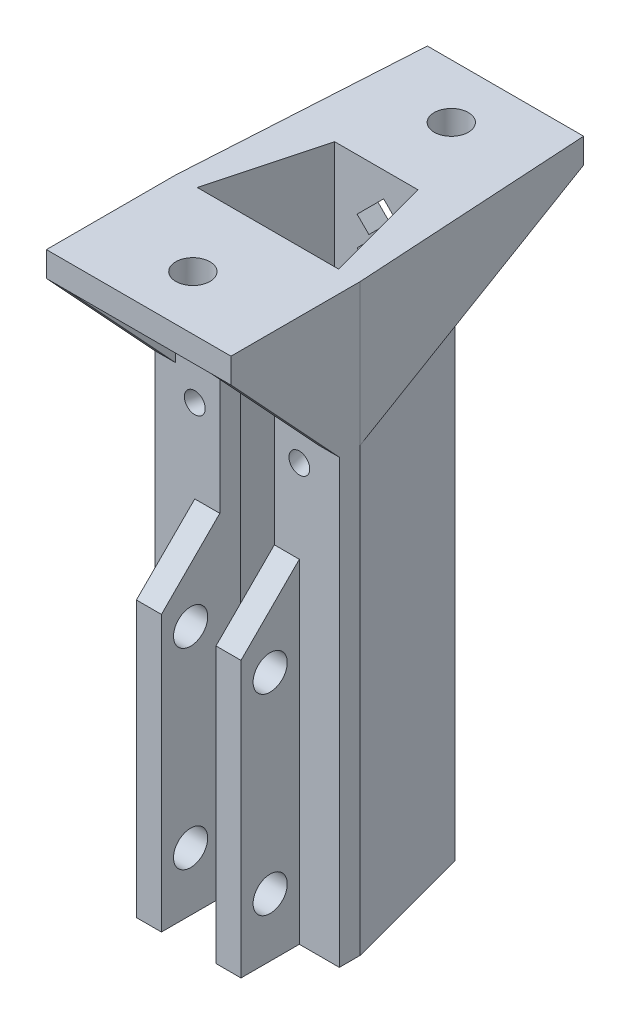
SolidWorks part; units mm, degrees
ref_plane "Front Plane" through (0, 0, 0) normal (0, 0, 1) x (1, 0, 0)
ref_plane "Top Plane" through (0, 0, 0) normal (0, 1, 0) x (1, 0, 0)
ref_plane "Right Plane" through (0, 0, 0) normal (1, 0, 0) x (0, 0, -1)
sketch "Sketch2" plane through (0, 0, 0) normal (0, 1, 0) x (1, 0, 0)
  line L0 (-8.0683, 3.8436) -> (5.7683, 3.8436)
  line L1 (-8.0683, 3.8436) -> (-8.0683, 1.3436)
  line L2 (5.7683, 3.8436) -> (5.7683, 1.3436)
  line L3 (-8.0683, 1.3436) -> (5.7683, 1.3436)
  line L4 (5.7683, 3.8436) -> (9.9215, -11.6564)
  line L5 (5.7683, 3.8436) -> (3.3535, 3.1965)
  line L6 (9.9215, -11.6564) -> (7.5067, -12.3035)
  line L7 (3.3535, 3.1965) -> (7.5067, -12.3035)
  line L8 (-8.0683, 3.8436) -> (-12.2215, -11.6564)
  line L9 (-8.0683, 3.8436) -> (-5.6535, 3.1965)
  line L10 (-12.2215, -11.6564) -> (-9.8067, -12.3035)
  line L11 (-5.6535, 3.1965) -> (-9.8067, -12.3035)
  line L12 (-12.2215, -11.6564) -> (-4.4215, -11.6564)
  line L13 (-12.2215, -11.6564) -> (-12.2215, -14.1564)
  line L14 (-4.4215, -11.6564) -> (-4.4215, -14.1564)
  line L15 (-12.2215, -14.1564) -> (-4.4215, -14.1564)
  line L16 (9.9215, -11.6564) -> (2.1215, -11.6564)
  line L17 (9.9215, -11.6564) -> (9.9215, -14.1564)
  line L18 (2.1215, -11.6564) -> (2.1215, -14.1564)
  line L19 (9.9215, -14.1564) -> (2.1215, -14.1564)
  line L20 (-4.4215, -14.1564) -> (-7.4215, -14.1564)
  line L21 (-4.4215, -14.1564) -> (-4.4215, -21.1564)
  line L22 (-7.4215, -14.1564) -> (-7.4215, -21.1564)
  line L23 (-4.4215, -21.1564) -> (-7.4215, -21.1564)
  line L24 (2.1215, -14.1564) -> (5.1215, -14.1564)
  line L25 (2.1215, -14.1564) -> (2.1215, -21.1564)
  line L26 (5.1215, -14.1564) -> (5.1215, -21.1564)
  line L27 (2.1215, -21.1564) -> (5.1215, -21.1564)
  point P0 (-6.15, 1.3436)
  point P21 (3.85, 1.3436)
  point P24 (7.3334, -11.6564)
  point P25 (-9.6333, -11.6564)
  dimension "D1" = 0
  dimension "D2" = 2.5
  dimension "D3" = 2.5
  dimension "D4" = 2.5
  dimension "D5" = 10
  dimension "D6" = 360
  dimension "D7" = 13
  dimension "D8" = 2.5
  dimension "D9" = 2.5
  dimension "D10" = 13
  dimension "D11" = 3
  dimension "D12" = 3
  dimension "D13" = 105
  dimension "D14" = 7.8
  dimension "D15" = 7.8
  dimension "D16" = 105
  dimension "D17" = 16.9667
  dimension "D18" = 6.5431
  dimension "D19" = 7
  dimension "D20" = 7
extrude "Boss-Extrude1" add sketch "Sketch2" along normal blind 40 contours L16 L4 L2 L3 L7 | L9 L11 L3 L7 L5 L0 | L8 L12 L11 L3 L1 | L5 L7 L3 L2 | L11 L9 L1 L3 | L13 L15 L14 L12 L11 L10 | L12 L10 L11 | L6 L16 L7 | L19 L17 L6 L7 L16 L18 | L25 L27 L26 L19 | L23 L21 L15 L22 region at (-7.0264, 0, -2.4857) region at (-9.164, 0, 4.9784) region at (-1.15, 0, -2.635) region at (6.8641, 0, 4.9784) region at (4.7264, 0, -2.4857) region at (-10.5538, 0, 11.8721) region at (-8.2214, 0, 12.9528) region at (5.9214, 0, 12.9528) region at (8.2539, 0, 11.8721) region at (-5.9215, 0, 17.6564) region at (3.6215, 0, 17.6564)
sketch "Sketch3" plane through (-7.4215, 0, 0) normal (-1, 0, 0) x (0, 0, 1)
  line L0 (21.1564, 40) -> (21.1564, 0) construction
  line L1 (14.1564, 40) -> (14.1564, 0) construction
  line L2 (14.1564, 40) -> (21.1564, 40) construction
  line L3 (14.1564, 0) -> (21.1564, 0) construction
  circle A0 centre (17.6564, 30) radius 2.05
  circle A1 centre (17.6564, 7) radius 2.05
  dimension "D5" = 4.1
  dimension "D6" = 4.1
  dimension "D1" = 3.5
  dimension "D2" = 3.5
  dimension "D3" = 3.5
  dimension "D4" = 3.5
  dimension "D7" = 10
  dimension "D8" = 7
extrude "Cut-Extrude2" cut sketch "Sketch3" against normal blind 40
sketch "Sketch4" plane through (0, 40, 0) normal (0, 1, 0) x (1, 0, 0)
  line L0 (-9.6333, -11.6564) -> (-6.15, 1.3436)
  line L1 (-6.15, 1.3436) -> (3.85, 1.3436)
  line L2 (3.85, 1.3436) -> (7.3334, -11.6564)
  line L3 (7.3334, -11.6564) -> (2.1215, -11.6564)
  line L4 (2.1215, -11.6564) -> (2.1215, -14.1564)
  line L5 (2.1215, -11.6564) -> (2.1215, -21.1564) construction
  line L6 (2.1215, -14.1564) -> (9.9215, -14.1564)
  line L7 (9.9215, -14.1564) -> (9.9215, -11.6564)
  line L8 (9.9215, -11.6564) -> (5.7683, 3.8436)
  line L9 (5.7683, 3.8436) -> (-8.0683, 3.8436)
  line L10 (-8.0683, 3.8436) -> (-12.2215, -11.6564)
  line L11 (-12.2215, -11.6564) -> (-12.2215, -14.1564)
  line L12 (-12.2215, -14.1564) -> (-4.4215, -14.1564)
  line L13 (-4.4215, -11.6564) -> (-4.4215, -21.1564) construction
  line L14 (-4.4215, -14.1564) -> (-4.4215, -11.6564)
  line L33 (-6.15, 1.3436) -> (3.85, 1.3436)
  line L34 (3.85, 1.3436) -> (7.3334, -11.6564)
  line L35 (7.3334, -11.6564) -> (2.1215, -11.6564)
  line L36 (2.1215, -11.6564) -> (2.1215, -21.1564)
  line L37 (2.1215, -21.1564) -> (5.1215, -21.1564)
  line L38 (5.1215, -21.1564) -> (5.1215, -14.1564)
  line L39 (5.1215, -14.1564) -> (9.9215, -14.1564)
  line L40 (9.9215, -14.1564) -> (9.9215, -11.6564)
  line L41 (9.9215, -11.6564) -> (5.7683, 3.8436)
  line L42 (5.7683, 3.8436) -> (-8.0683, 3.8436)
  line L43 (-8.0683, 3.8436) -> (-12.2215, -11.6564)
  line L44 (-12.2215, -11.6564) -> (-12.2215, -14.1564)
  line L45 (-12.2215, -14.1564) -> (-7.4215, -14.1564)
  line L46 (-7.4215, -14.1564) -> (-7.4215, -21.1564)
  line L47 (-7.4215, -21.1564) -> (-4.4215, -21.1564)
  line L48 (-4.4215, -21.1564) -> (-4.4215, -11.6564)
  line L49 (-4.4215, -11.6564) -> (-9.6333, -11.6564)
  line L50 (-9.6333, -11.6564) -> (-6.15, 1.3436)
  line L51 (-6.15, 1.3436) -> (3.85, 1.3436)
  line L52 (3.85, 1.3436) -> (7.3334, -11.6564)
  line L53 (7.3334, -11.6564) -> (2.1215, -11.6564)
  line L54 (2.1215, -11.6564) -> (2.1215, -21.1564)
  line L55 (2.1215, -21.1564) -> (5.1215, -21.1564)
  line L56 (5.1215, -21.1564) -> (5.1215, -14.1564)
  line L57 (5.1215, -14.1564) -> (9.9215, -14.1564)
  line L58 (9.9215, -14.1564) -> (9.9215, -11.6564)
  line L59 (9.9215, -11.6564) -> (5.7683, 3.8436)
  line L60 (5.7683, 3.8436) -> (-8.0683, 3.8436)
  line L61 (-8.0683, 3.8436) -> (-12.2215, -11.6564)
  line L62 (-12.2215, -11.6564) -> (-12.2215, -14.1564)
  line L63 (-12.2215, -14.1564) -> (-7.4215, -14.1564)
  line L64 (-7.4215, -14.1564) -> (-7.4215, -21.1564)
  line L65 (-7.4215, -21.1564) -> (-4.4215, -21.1564)
  line L66 (-4.4215, -21.1564) -> (-4.4215, -11.6564)
  line L68 (-9.6333, -11.6564) -> (-6.15, 1.3436)
  line M19 (-6.15, 1.3436) -> (3.85, 1.3436)
  line M20 (3.85, 1.3436) -> (7.3334, -11.6564)
  line M21 (7.3334, -11.6564) -> (2.1215, -11.6564)
  line M22 (2.1215, -11.6564) -> (2.1215, -21.1564)
  line M25 (5.1215, -14.1564) -> (9.9215, -14.1564)
  line M26 (9.9215, -14.1564) -> (9.9215, -11.6564)
  line M27 (9.9215, -11.6564) -> (5.7683, 3.8436)
  line M28 (5.7683, 3.8436) -> (-8.0683, 3.8436)
  line M29 (-8.0683, 3.8436) -> (-12.2215, -11.6564)
  line M30 (-12.2215, -11.6564) -> (-12.2215, -14.1564)
  line M31 (-12.2215, -14.1564) -> (-7.4215, -14.1564)
  line M34 (-4.4215, -21.1564) -> (-4.4215, -11.6564)
  line M35 (-4.4215, -11.6564) -> (-9.6333, -11.6564)
  line M36 (-9.6333, -11.6564) -> (-6.15, 1.3436)
  dimension "D1" = 0
extrude "Boss-Extrude2" add sketch "Sketch4" along normal blind 30 contours L12 L6 M31 M34 M35 M36 M19 M20 M21 M22 M25 M26 M27 M28 M29 M30 region at (-7.0274, 40, 11.9418)
sketch "Sketch16" plane through (0, 0, 14.1564) normal (0, 0, 1) x (1, 0, 0)
  line L0 (-4.4215, 70) -> (-4.4215, 40) construction
  line L1 (-12.2215, 70) -> (-4.4215, 70) construction
  circle A0 centre (-7.4215, 50) radius 1.25
  dimension "D1" = 20
  dimension "D2" = 2.5
  dimension "D4" = 3
extrude "Cut-Extrude9" cut sketch "Sketch16" along direction (-0.2588, 0, 0.9659) on the side against the normal blind 3.5
sketch "Sketch17" plane through (0, 0, 14.1564) normal (0, 0, 1) x (1, 0, 0)
  line L0 (2.1215, 70) -> (2.1215, 40) construction
  line L1 (2.1215, 70) -> (9.9215, 70) construction
  circle A0 centre (5.1215, 50) radius 1.25
  dimension "D1" = 2.5
  dimension "D2" = 3
  dimension "D3" = 20
extrude "Cut-Extrude10" cut sketch "Sketch17" along direction (0.2588, 0, 0.9659) on the side against the normal blind 3.5
sketch "Sketch18" plane through (0, 0, 11.6564) normal (0, 0, -1) x (-1, 0, 0)
  line L0 (-9.9215, 70) -> (-9.9215, 0) construction
  line L1 (-9.9215, 70) -> (12.2215, 70)
  line L2 (-9.9215, 70) -> (-9.9215, 67)
  line L3 (-9.9215, 67) -> (12.2215, 67)
  line L4 (12.2215, 70) -> (12.2215, 67)
  line L5 (12.2215, 70) -> (12.2215, 0) construction
  dimension "D1" = 3
  dimension "D2" = 0
extrude "Boss-Extrude4" add sketch "Sketch18" against normal blind 15.5
sketch "Sketch19" plane through (0, 0, -3.8436) normal (0, 0, -1) x (-1, 0, 0)
  line L0 (-5.7683, 70) -> (-5.7683, 0) construction
  line L1 (8.0683, 70) -> (-5.7683, 70)
  line L2 (8.0683, 70) -> (8.0683, 67)
  line L3 (8.0683, 67) -> (-5.7683, 67)
  line L4 (-5.7683, 70) -> (-5.7683, 67)
  dimension "D1" = 3
extrude "Boss-Extrude5" add sketch "Sketch19" along normal blind 13 and the other way blind 2 contours L1 L4 L3 L2
sketch "Sketch21" plane through (-12.2215, 0, 0) normal (-1, 0, 0) x (0, 0, 1)
  line L0 (27.1564, 67) -> (14.1564, 53)
  line L1 (14.1564, 67) -> (14.1564, 0) construction
  line L2 (14.1564, 53) -> (14.1564, 67)
  line L3 (14.1564, 67) -> (27.1564, 67)
  dimension "D1" = 14
extrude "Boss-Extrude6" add sketch "Sketch21" against normal blind 2.5
sketch "Sketch22" plane through (9.9215, 0, 0) normal (1, 0, 0) x (0, 0, -1)
  line L0 (-27.1564, 67) -> (-14.1564, 67)
  line L1 (-14.1564, 67) -> (-14.1564, 53)
  line L2 (-14.1564, 67) -> (-14.1564, 0) construction
  line L3 (-14.1564, 53) -> (-27.1564, 67)
  dimension "D1" = 14
extrude "Boss-Extrude8" add sketch "Sketch22" against normal blind 2.5
sketch "Sketch23" plane through (9.9215, 0, 0) normal (1, 0, 0) x (0, 0, -1)
  line L0 (-11.6564, 70) -> (-11.6564, 53)
  line L1 (-11.6564, 70) -> (-11.6564, 0) construction
  line L2 (16.8436, 70) -> (16.8436, 67)
  line L3 (16.8436, 70) -> (-11.6564, 70)
  line L4 (16.8436, 67) -> (-11.6564, 53)
  dimension "D1" = 28.5
  dimension "D2" = 28.5
  dimension "D3" = 17
  dimension "D4" = 3
extrude "Boss-Extrude9" add sketch "Sketch23" against normal blind 4.2
sketch "Sketch24" plane through (-12.2215, 0, 0) normal (-1, 0, 0) x (0, 0, 1)
  line L0 (11.6564, 70) -> (-16.8436, 70)
  line L1 (-16.8436, 70) -> (-16.8436, 67)
  line L2 (-16.8436, 67) -> (11.6564, 53)
  line L3 (11.6564, 70) -> (11.6564, 0) construction
  line L4 (11.6564, 53) -> (11.6564, 70)
  dimension "D1" = 17
  dimension "D2" = 28.5
  dimension "D3" = 3
extrude "Boss-Extrude10" add sketch "Sketch24" against normal blind 4.2
sketch "Sketch25" plane through (0, 70, 0) normal (0, 1, 0) x (1, 0, 0)
  line L2 (-6.15, 1.3436) -> (3.85, 1.3436) construction
  line L3 (5.7215, -11.6564) -> (-8.0215, -11.6564) construction
  circle A0 centre (-1.15, 10.3436) radius 2.05
  circle A1 centre (-1.15, -20.6564) radius 2.05
  dimension "D1" = 4.1
  dimension "D2" = 4.1
  dimension "D3" = 9
  dimension "D4" = 9
  dimension "D5" = 6.8715
  dimension "D6" = 6.8715
  dimension "D7" = 5
  dimension "D8" = 5
extrude "Cut-Extrude12" cut sketch "Sketch25" against normal blind 3.5
sketch "Sketch26" plane through (0, 47.3099, 23.2399) normal (0, -0.8976, -0.4409) x (-1, 0, 0)
  line L0 (-5.7215, 12.9056) -> (-7.3334, 12.9056)
  line L1 (-7.3334, 12.9056) -> (-5.7215, 19.6076)
  line L2 (-5.7215, 19.6076) -> (-5.7215, 12.9056)
  line L3 (8.0215, 12.9056) -> (8.0215, 19.6076)
  line L4 (8.0215, 19.6076) -> (9.6333, 12.9056)
  line L5 (9.6333, 12.9056) -> (8.0215, 12.9056)
extrude "Cut-Extrude13" cut sketch "Sketch26" along direction (0, -1, 0) on the side against the normal through all
sketch "Sketch27" plane through (0, 47.3099, 23.2399) normal (0, -0.8976, -0.4409) x (-1, 0, 0)
  line L0 (12.2215, 12.9056) -> (10.5215, 44.6586)
  line L1 (12.2215, 44.6586) -> (8.0215, 44.6586) construction
  line L2 (10.5215, 44.6586) -> (12.2215, 44.6586)
  line L3 (12.2215, 44.6586) -> (12.2215, 12.9056)
  line L4 (-9.9215, 12.9056) -> (-9.9215, 44.6586)
  line L5 (-9.9215, 44.6586) -> (-8.2215, 44.6586)
  line L6 (-5.7215, 44.6586) -> (-9.9215, 44.6586) construction
  line L7 (-8.2215, 44.6586) -> (-9.9215, 12.9056)
  dimension "D1" = 2.5
  dimension "D2" = 2.5
extrude "Cut-Extrude14" cut sketch "Sketch27" along direction (0, -1, 0) on the side against the normal through all
sketch "Sketch29" plane through (0, 67, 0) normal (0, -1, 0) x (1, 0, 0)
  line L1 (2.1215, 11.6564) -> (-4.4215, 11.6564)
  line L2 (2.1215, 11.6564) -> (2.1215, 14.1564)
  line L3 (2.1215, 14.1564) -> (-4.4215, 14.1564)
  line L4 (-4.4215, 11.6564) -> (-4.4215, 14.1564)
extrude "Boss-Extrude12" add sketch "Sketch29" along normal blind 12
sketch "Sketch30" plane through (0, 0, 14.1564) normal (0, 0, 1) x (1, 0, 0)
  line L0 (-0.2661, 67) -> (-3.4481, 63.818)
  line L1 (-0.2661, 67) -> (1.1481, 65.5858)
  line L2 (-3.4481, 63.818) -> (-2.0339, 62.4038)
  line L3 (1.1481, 65.5858) -> (-2.0339, 62.4038)
  line L4 (-3.4481, 60.318) -> (-2.0339, 58.9038)
  line L5 (-0.2661, 63.5) -> (-3.4481, 60.318)
  line L6 (-9.7215, 67) -> (7.4215, 67) construction
  line L7 (1.1481, 65.5858) -> (-3.4481, 63.818) construction
  line L8 (-2.0339, 62.4038) -> (-0.2661, 67) construction
  line L9 (7.4215, 53) -> (7.4215, 67) construction
  line L10 (-9.7215, 67) -> (-9.7215, 53) construction
  line L11 (1.1481, 62.0858) -> (-2.0339, 58.9038)
  line L12 (-0.2661, 63.5) -> (1.1481, 62.0858)
  line L13 (-3.4481, 56.818) -> (-2.0339, 55.4038)
  line L14 (-0.2661, 60) -> (-3.4481, 56.818)
  line L15 (1.1481, 58.5858) -> (-2.0339, 55.4038)
  line L16 (-0.2661, 60) -> (1.1481, 58.5858)
  point P0 (-1.15, 64.7019)
  dimension "D1" = 2
  dimension "D2" = 4.5
  dimension "D3" = 2
  dimension "D4" = 4.5
  dimension "D5" = 45
  dimension "D6" = 17.1431
  dimension "D7" = 3.2715
  dimension "D8" = 3.2716
  dimension "D9" = 90
  dimension "D10" = 90
  dimension "D11" = 3
extrude "Cut-Extrude15" cut sketch "Sketch30" against normal through all
fillet "Fillet1" radius 1 2 edges at (-4.4215, 55, 12.9064) (2.1215, 55, 12.9064)
sketch "Sketch31" plane through (5.1215, 0, 0) normal (1, 0, 0) x (0, 0, -1)
  line L0 (-14.1564, 40) -> (-21.1564, 40)
  line L1 (-21.1564, 40) -> (-21.1564, 33)
  line L2 (-21.1564, 40) -> (-21.1564, 0) construction
  line L3 (-21.1564, 33) -> (-14.1564, 40)
  dimension "D1" = 45
extrude "Cut-Extrude16" cut sketch "Sketch31" against normal blind 18
